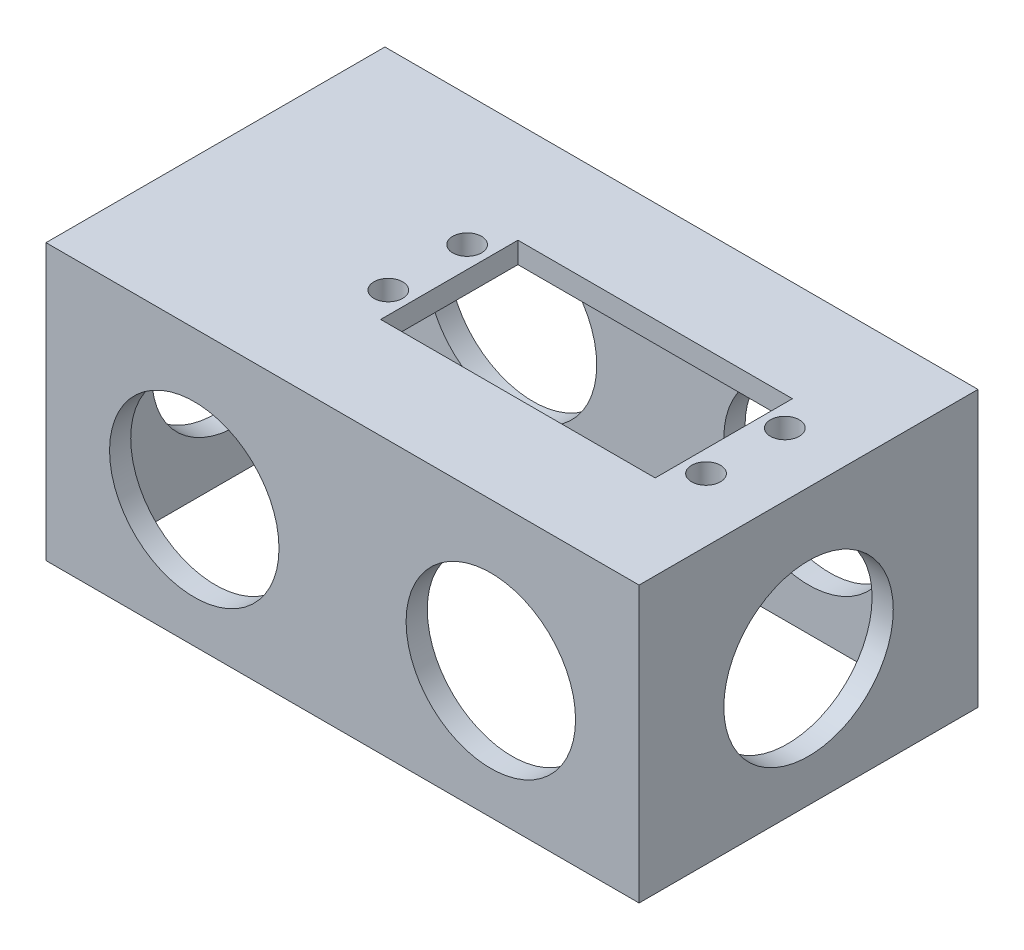
SolidWorks part; units mm, degrees
ref_plane "Front" through (0, 0, 0) normal (0, 0, 1) x (1, 0, 0)
ref_plane "Top" through (0, 0, 0) normal (0, 1, 0) x (1, 0, 0)
ref_plane "Right" through (0, 0, 0) normal (1, 0, 0) x (0, 0, -1)
sketch "Sketch3" plane through (0, 0, 0) normal (0, 1, 0) x (1, 0, 0)
  line L0 (3.175, 3.175) -> (85.725, 3.175)
  line L1 (0, 0) -> (88.9, 0)
  line L2 (0, 0) -> (0, 50.8)
  line L3 (0, 50.8) -> (88.9, 50.8)
  line L4 (88.9, 0) -> (88.9, 50.8)
  line L5 (85.725, 3.175) -> (85.725, 47.625)
  line L6 (3.175, 47.625) -> (85.725, 47.625)
  line L7 (3.175, 3.175) -> (3.175, 47.625)
  dimension "D1" = 88.9
  dimension "D2" = 50.8
  dimension "D3" = 3.175
extrude "Boss-Extrude2" add sketch "Sketch3" along normal blind 38.1
sketch "Sketch4" plane through (88.9, 0, 0) normal (1, 0, 0) x (0, 0, -1)
  line L2 (0, 38.1) -> (50.8, 38.1) construction
  line L3 (25.4, 19.05) -> (25.4, 38.1) construction
  line L4 (25.4, 19.05) -> (50.8, 19.05) construction
  line L5 (50.8, 38.1) -> (50.8, 0) construction
  circle A0 centre (25.4, 19.05) radius 12.7
  dimension "D1" = 25.4
extrude "Cut-Extrude1" cut sketch "Sketch4" against normal up to surface (88.9 mm away) up to face at (0, 19.05, -25.4)
sketch "Sketch6" plane through (0, 38.1, 0) normal (0, 1, 0) x (1, 0, 0)
  line L1 (88.9, 50.8) -> (0, 50.8)
  line L2 (88.9, 50.8) -> (88.9, 0)
  line L3 (88.9, 0) -> (0, 0)
  line L4 (0, 50.8) -> (0, 0)
extrude "Boss-Extrude3" add sketch "Sketch6" along normal blind 3.175
sketch "Sketch7" plane through (0, 0, -50.8) normal (0, 0, -1) x (-1, 0, 0)
  line L0 (-44.45, 41.275) -> (-44.45, 0) construction
  line L1 (-88.9, 41.275) -> (0, 41.275) construction
  line L2 (-88.9, 0) -> (0, 0) construction
  line L3 (0, 19.05) -> (-76.2, 19.05) construction
  line L6 (-22.225, 19.05) -> (-22.225, 41.275) construction
  line L7 (-44.45, 41.275) -> (0, 41.275) construction
  line L8 (-88.9, 41.275) -> (-44.45, 41.275) construction
  line L9 (-66.675, 19.05) -> (-66.675, 41.275) construction
  circle A0 centre (-66.675, 19.05) radius 12.7
  circle A1 centre (-22.225, 19.05) radius 12.7
  point P19 (-22.225, 41.275)
  dimension "D1" = 25.4
  dimension "D2" = 19.05
extrude "Cut-Extrude2" cut sketch "Sketch7" against normal up to surface (50.8 mm away) up to face at (44.45, 20.6375, 0)
sketch "Sketch8" plane through (0, 41.275, 0) normal (0, 1, 0) x (1, 0, 0)
  line L0 (44.45, 0) -> (44.45, 50.8) construction
  line L1 (76.2, 15.113) -> (35.052, 15.113)
  line L2 (76.2, 15.113) -> (76.2, 35.687)
  line L3 (76.2, 35.687) -> (35.052, 35.687)
  line L4 (35.052, 15.113) -> (35.052, 35.687)
  line L5 (0, 0) -> (88.9, 0) construction
  line L6 (88.9, 50.8) -> (0, 50.8) construction
  point P10 (35.052, 25.4)
  point P11 (44.45, 25.4)
  point P12 (28.2575, 25.4)
  point P13 (55.626, 15.5575)
  point P14 (55.626, 15.113)
  line B0 (28.2575, 35.2425) -> (28.2575, 15.5575) construction
  line B1 (28.2575, 15.5575) -> (82.9945, 15.5575) construction
  circle B2 centre (31.8135, 31.3055) radius 2.159
  circle B3 centre (31.8135, 19.4945) radius 2.159
  circle B4 centre (79.4385, 19.4945) radius 2.159
  circle B5 centre (79.4385, 31.3055) radius 2.159
  dimension "D1" = 9.398
  dimension "D2" = 41.148
  dimension "D3" = 20.574
sketch_block_instance "ServoMountingHoles-1"
sketch_block "ServoMountingHoles"
extrude "Cut-Extrude3" cut sketch "Sketch8" against normal up to next
